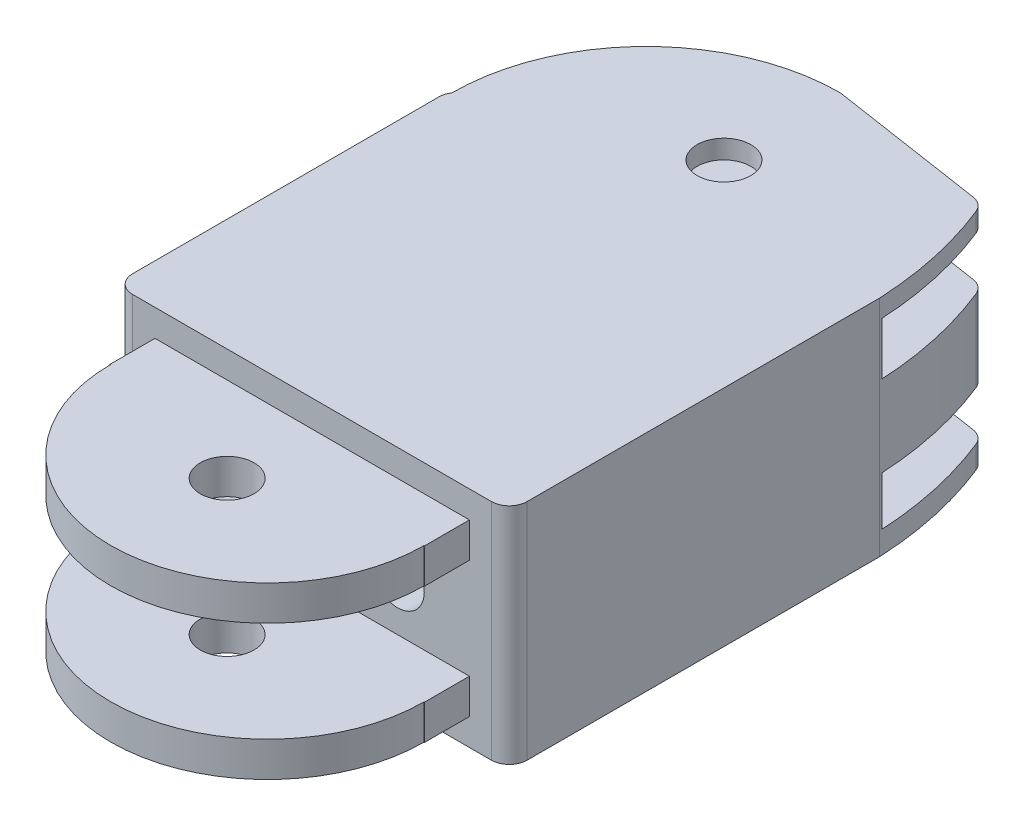
SolidWorks part; units mm, degrees
ref_plane "Front Plane" through (0, 0, 0) normal (0, 0, 1) x (1, 0, 0)
ref_plane "Top Plane" through (0, 0, 0) normal (0, 1, 0) x (1, 0, 0)
ref_plane "Right Plane" through (0, 0, 0) normal (1, 0, 0) x (0, 0, -1)
sketch "Sketch2" plane through (0, 0, 0) normal (0, 0, 1) x (1, 0, 0)
  line L0 (-24.2561, -24.0702) -> (-22.0061, -24.0702) construction
  line L1 (-24.2561, -17.8202) -> (-2.2017, -17.8202) construction
  line L2 (-24.2561, -17.8202) -> (-24.2561, -30.3202) construction
  line L3 (-24.2561, -30.3202) -> (-2.2017, -30.3202) construction
  line L4 (-2.2017, -17.8202) -> (-2.2017, -30.3202) construction
  line L5 (-2.2017, -24.0702) -> (-4.4517, -24.0702) construction
  line L6 (-22.0061, -24.0702) -> (-22.0061, -30.3202) construction
  line L7 (-4.4517, -24.0702) -> (-4.4517, -30.3202) construction
  line L8 (-24.2561, -17.8202) -> (-24.2561, -19.3148) construction
  line L9 (-24.2561, -19.3148) -> (-22.0061, -19.3148) construction
  line L10 (-2.2017, -17.8202) -> (-2.2017, -19.3148) construction
  line L11 (-2.2017, -19.3148) -> (-4.4517, -19.3148) construction
  line L12 (-2.2017, -30.3202) -> (-2.2017, -28.8202) construction
  line L13 (-2.2017, -28.8202) -> (-4.4517, -28.8202) construction
  line L14 (-24.2561, -30.3202) -> (-24.2561, -28.8202) construction
  line L15 (-24.2561, -28.8202) -> (-22.0061, -28.8202) construction
  line L17 (-22.0061, -28.8202) -> (-4.4517, -28.8202)
  line L18 (-22.0061, -28.8202) -> (-22.0061, -26.8702)
  line L19 (-22.0061, -26.8702) -> (-4.4517, -26.8702)
  line L20 (-4.4517, -28.8202) -> (-4.4517, -26.8702)
  line L21 (-22.0061, -28.8202) -> (-4.4517, -26.8702) construction
  line L22 (-22.0061, -26.8702) -> (-4.4517, -28.8202) construction
  line L23 (-22.0061, -19.3148) -> (-4.4517, -19.3148)
  line L24 (-22.0061, -19.3148) -> (-22.0061, -21.2648)
  line L25 (-22.0061, -21.2648) -> (-4.4517, -21.2648)
  line L26 (-4.4517, -19.3148) -> (-4.4517, -21.2648)
  line L27 (-22.0061, -19.3148) -> (-4.4517, -21.2648) construction
  line L28 (-22.0061, -21.2648) -> (-4.4517, -19.3148) construction
  point P19 (-13.2289, -27.8452)
  point P22 (-13.2289, -20.2898)
extrude "Boss-Extrude1" add sketch "Sketch2" along normal blind 8.75
sketch "Sketch3" plane through (0, -19.3148, 0) normal (0, 1, 0) x (1, 0, 0)
  line L0 (-4.4517, 0) -> (-22.0061, 0) construction
  line L1 (-4.4517, -8.75) -> (-22.0061, -8.75) construction
  arc A0 (-13.2289, -8.75) -> (-4.4789, 0) centre (-13.2289, 0) ccw
  arc A1 (-13.2289, -8.75) -> (-21.9789, 0) centre (-13.2289, 0) cw
  spline S0 degree 2 poles (-22.0061, -8.75) (-13.2289, -12.4735) (-4.4517, -8.75) knots 0 0 0 1 1 1
  spline S1 degree 2 poles (-21.9789, 0) (-25.927, -4.2429) (-22.0061, -8.75) knots 0 0 0 1 1 1
  spline S2 degree 2 poles (-4.4789, 0) (1.1383, -4.1517) (-4.4517, -8.75) knots 0 0 0 1 1 1
extrude "Cut-Extrude1" cut sketch "Sketch3" against normal through all contours S0 S2 A0 A1 S1
sketch "Sketch4" plane through (0, 0, 0) normal (0, 0, -1) x (-1, 0, 0)
  line L0 (22.0061, -19.3148) -> (24.2561, -19.3148) construction
  line L1 (22.0061, -19.3148) -> (4.4789, -19.3148) construction
  line L2 (22.0061, -19.3148) -> (22.0061, -28.8202) construction
  line L3 (22.0061, -28.8202) -> (4.4789, -28.8202) construction
  line L4 (4.4789, -19.3148) -> (4.4789, -28.8202) construction
  line L5 (22.0061, -19.3148) -> (4.4789, -28.8202) construction
  line L6 (22.0061, -28.8202) -> (4.4789, -19.3148) construction
  line L7 (24.2561, -19.3148) -> (24.2561, -17.8148) construction
  line L8 (4.4789, -28.8202) -> (2.2289, -28.8202) construction
  line L9 (2.2289, -28.8202) -> (2.2289, -30.3202) construction
  line L11 (24.2561, -17.8148) -> (2.2289, -17.8148)
  line L12 (24.2561, -17.8148) -> (24.2561, -30.3202)
  line L13 (24.2561, -30.3202) -> (2.2289, -30.3202)
  line L14 (2.2289, -17.8148) -> (2.2289, -30.3202)
  line L15 (24.2561, -17.8148) -> (2.2289, -30.3202) construction
  line L16 (24.2561, -30.3202) -> (2.2289, -17.8148) construction
  point P4 (13.2425, -24.0675)
  point P14 (13.2425, -24.0675)
extrude "Boss-Extrude2" add sketch "Sketch4" along normal blind 32 contours L12 L13 L14 L11
sketch "Sketch5" plane through (0, -19.3148, 0) normal (0, 1, 0) x (1, 0, 0)
  line L0 (-13.2289, -8.75) -> (-13.2289, -2.25) construction
  arc A0 (-21.9789, 0) -> (-4.4789, 0) centre (-13.2289, 0) ccw construction
  circle A1 centre (-13.2289, -2.25) radius 1.5
extrude "Cut-Extrude2" cut sketch "Sketch5" against normal blind 12 contours A1
sketch "Sketch6" plane through (0, 0, 0) normal (0, 0, 1) x (1, 0, 0)
  line L0 (-24.2561, -30.3202) -> (-2.2289, -30.3202)
  line L1 (-2.2289, -30.3202) -> (-2.2289, -17.8148)
  line L2 (-2.2289, -17.8148) -> (-24.2561, -17.8148)
  line L3 (-24.2561, -17.8148) -> (-24.2561, -30.3202)
  line L4 (-22.0061, -28.8202) -> (-4.4517, -28.8202)
  line L5 (-4.4517, -28.8202) -> (-4.4517, -26.8702)
  line L6 (-4.4517, -28.8202) -> (-4.4517, -26.8702) construction
  line L7 (-4.4517, -26.8702) -> (-22.0061, -26.8702)
  line L8 (-22.0061, -28.8202) -> (-22.0061, -26.8702)
  line L9 (-22.0061, -21.2648) -> (-22.0061, -19.3148)
  line L10 (-22.0061, -19.3148) -> (-4.4517, -19.3148)
  line L11 (-4.4517, -19.3148) -> (-4.4517, -21.2648)
  line L12 (-4.4517, -21.2648) -> (-22.0061, -21.2648)
extrude "Cut-Extrude3" cut sketch "Sketch6" against normal blind 2.5
sketch "Sketch7" plane through (0, -17.8148, 0) normal (0, 1, 0) x (1, 0, 0)
  line L0 (-13.2425, 32) -> (-13.2425, 25.5) construction
  line L1 (-24.2561, 32) -> (-2.2289, 32) construction
  line L2 (-13.2425, 25.5) -> (-13.2425, 21.1557) construction
  line L3 (-24.0869, 21.1557) -> (-24.2561, 21.1557)
  line L4 (-24.2561, 32) -> (-24.2561, 2.5) construction
  line L6 (-2.2289, 32) -> (-2.2289, 2.5) construction
  line L7 (-13.2425, 32) -> (-3.9485, 30.5853)
  circle A0 centre (-13.2425, 25.5) radius 1.5
  arc A1 (-13.2425, 32) -> (-24.0869, 21.1557) centre (-13.2425, 21.1557) ccw
  spline S0 degree 3 poles (-2.2289, 21.1557) (11.4715, 27.1897) (-11.7652, 53.4313) (-37.0079, 21.5236) (-24.2561, 21.1557) knots 0 0 0 0 0.520113 1 1 1 1
  spline S1 degree 2 poles (-3.9485, 30.5853) (-2.0071, 26.0937) (-2.2289, 21.1557) knots 0 0 0 1 1 1
extrude "Cut-Extrude4" cut sketch "Sketch7" against normal blind 13
sketch "Sketch8" plane through (0, 0, -2.5) normal (0, 0, 1) x (1, 0, 0)
  line L0 (-24.2561, -24.0675) -> (-18.0111, -24.0675) construction
  line L1 (-24.2561, -17.8148) -> (-24.2561, -30.3202) construction
  line L2 (-2.2289, -24.0675) -> (-8.474, -24.0675) construction
  line L3 (-2.2289, -30.3202) -> (-2.2289, -17.8148) construction
  line L4 (-4.4517, -21.2648) -> (-4.4517, -24.0675) construction
  line L5 (-4.4517, -24.0675) -> (-8.474, -24.0675) construction
  circle A0 centre (-18.0111, -24.0675) radius 1.5
  circle A1 centre (-8.474, -24.0675) radius 1.5
extrude "Cut-Extrude5" cut sketch "Sketch8" against normal blind 34
fillet "Fillet3" radius 1 4 edges at (-24.2561, -24.0675, -2.5) (-24.2561, -24.0675, -21.1557) (-2.2289, -24.0675, -2.5) (-3.9485, -24.0675, -30.5853)
ref_plane "Plane4" through (0, 0, -32.5) normal (0, 0, 1) x (1, 0, 0)
sketch "Sketch9" plane through (0, 0, -32.5) normal (0, 0, 1) x (1, 0, 0)
  line L0 (-24.248, -17.8194) -> (-24.248, -18.8664) construction
  line L1 (-24.248, -17.8194) -> (-2.2371, -17.8194) construction
  line L2 (-24.248, -17.8194) -> (-24.248, -30.3155) construction
  line L3 (-24.248, -30.3155) -> (-2.2371, -30.3155) construction
  line L4 (-2.2371, -17.8194) -> (-2.2371, -30.3155) construction
  line L5 (-24.248, -17.8194) -> (-2.2371, -30.3155) construction
  line L6 (-24.248, -30.3155) -> (-2.2371, -17.8194) construction
  line L7 (-24.248, -30.3155) -> (-24.248, -29.0658) construction
  line L8 (-24.248, -18.8664) -> (-2.2371, -18.8664)
  line L9 (-24.248, -18.8664) -> (-24.248, -21.7989)
  line L10 (-24.248, -21.7989) -> (-2.2371, -21.7989)
  line L11 (-2.2371, -18.8664) -> (-2.2371, -21.7989)
  line L12 (-24.248, -18.8664) -> (-2.2371, -21.7989) construction
  line L13 (-24.248, -21.7989) -> (-2.2371, -18.8664) construction
  line L14 (-13.2425, -26.3361) -> (-13.2425, -24.0675) construction
  line L15 (-24.248, -29.0658) -> (-2.2371, -29.0658)
  line L16 (-24.248, -29.0658) -> (-24.248, -26.3361)
  line L17 (-24.248, -26.3361) -> (-2.2371, -26.3361)
  line L18 (-2.2371, -29.0658) -> (-2.2371, -26.3361)
  line L19 (-24.248, -29.0658) -> (-2.2371, -26.3361) construction
  line L20 (-24.248, -26.3361) -> (-2.2371, -29.0658) construction
  line L21 (-13.2425, -24.0675) -> (-13.2425, -21.7989) construction
  point P4 (-13.2425, -24.0675)
  point P8 (-13.2425, -20.3326)
  point P13 (-13.2425, -27.7009)
  point P16 (0, 0)
  point P18 (-24.3721, -29.0658)
  point P19 (0, 0)
  point P20 (-24.248, -18.8664)
  point P22 (0, 0)
  point P23 (0, 0)
extrude "Cut-Extrude6" cut sketch "Sketch9" along normal blind 11
sketch "Sketch10" plane through (0, 0, -21.5) normal (0, 0, -1) x (-1, 0, 0)
  line L0 (2.2371, -18.8664) -> (24.0814, -18.8664) construction
  line L1 (22.2997, -18.8664) -> (3.8093, -18.8664)
  line L2 (22.2997, -18.8664) -> (22.2997, -21.7989)
  line L3 (22.2997, -21.7989) -> (3.8093, -21.7989)
  line L4 (3.8093, -18.8664) -> (3.8093, -21.7989)
  line L5 (22.2997, -18.8664) -> (3.8093, -21.7989) construction
  line L6 (22.2997, -21.7989) -> (3.8093, -18.8664) construction
  line L7 (24.0814, -21.7989) -> (2.2371, -21.7989) construction
  line L8 (2.2371, -26.3361) -> (24.0814, -26.3361) construction
  line L9 (3.8093, -26.3361) -> (22.2997, -26.3361)
  line L10 (3.8093, -26.3361) -> (3.8093, -29.0658)
  line L11 (3.8093, -29.0658) -> (22.2997, -29.0658)
  line L12 (22.2997, -26.3361) -> (22.2997, -29.0658)
  line L13 (3.8093, -26.3361) -> (22.2997, -29.0658) construction
  line L14 (3.8093, -29.0658) -> (22.2997, -26.3361) construction
  line L15 (24.0814, -29.0658) -> (2.2371, -29.0658) construction
  point P4 (13.0545, -20.3326)
  point P13 (13.0545, -27.7009)
extrude "Cut-Extrude7" cut sketch "Sketch10" against normal blind 5
